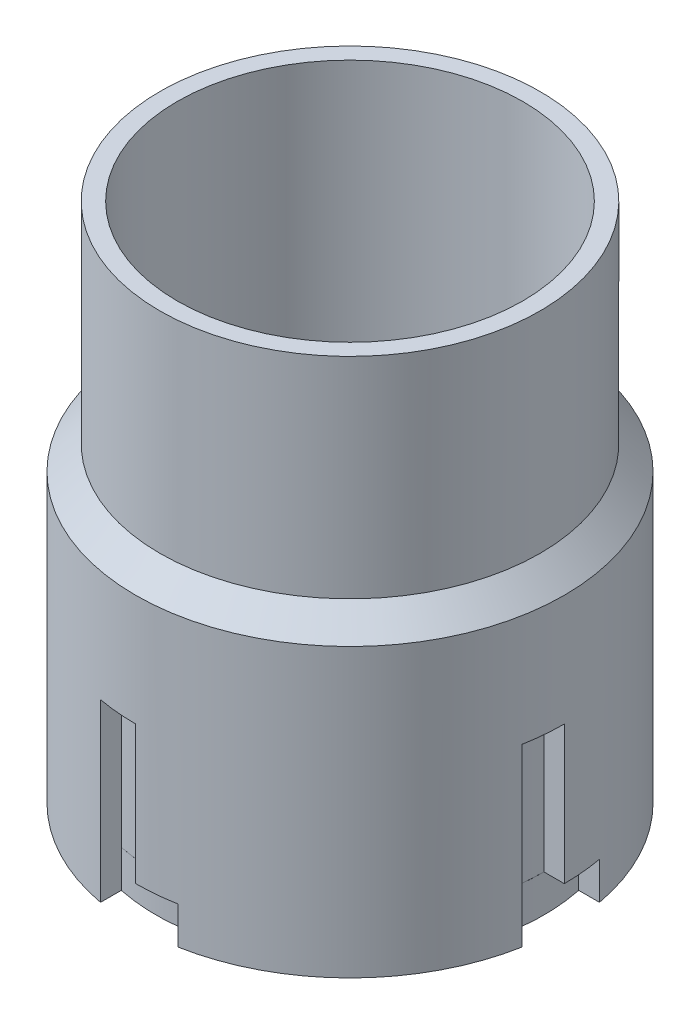
SolidWorks part; units mm, degrees
ref_plane "Front Plane" through (0, 0, 0) normal (0, 0, 1) x (1, 0, 0)
ref_plane "Top Plane" through (0, 0, 0) normal (0, 1, 0) x (1, 0, 0)
ref_plane "Right Plane" through (0, 0, 0) normal (1, 0, 0) x (0, 0, -1)
sketch "Sketch1" plane through (0, 0, 0) normal (0, 1, 0) x (1, 0, 0)
  circle A0 centre (0, 0) radius 39.37
  dimension "D1" = 78.74
extrude "Boss-Extrude1" add sketch "Sketch1" along normal blind 101.6
sketch "Sketch2" plane through (0, 101.6, 0) normal (0, 1, 0) x (1, 0, 0)
  circle A0 centre (0, 0) radius 31.75
extrude "Cut-Extrude1" cut sketch "Sketch2" against normal through all
sketch "Sketch3" plane through (0, 101.6, 0) normal (0, 1, 0) x (1, 0, 0)
  circle A0 centre (0, 0) radius 34.925
  circle A1 centre (0, 0) radius 39.37
  circle A2 centre (0, 0) radius 39.37 construction
extrude "Cut-Extrude2" cut sketch "Sketch3" against normal blind 33.02
sketch "Sketch5" plane through (0, 0, 0) normal (0, -1, 0) x (1, 0, 0)
  line L4 (-7.112, -34.9123) -> (-7.112, -38.7223)
  line L5 (7.112, -34.9123) -> (7.112, -38.7223)
  circle A0 centre (0, 0) radius 39.37 construction
  arc A4 (7.112, -34.9123) -> (-7.112, -34.9123) centre (0, -0.6458) cw
  arc A5 (-7.112, -38.7223) -> (7.112, -38.7223) centre (0, -0.6458) ccw
  dimension "D1" = 3.81
  dimension "D2" = 3.81
  dimension "D3" = 14.224
extrude "Cut-Extrude3" cut sketch "Sketch5" against normal blind 12.7
sketch3d "3DSketch4"
  point P0 (1.3658, 86.1586, 34.8983)
ref_plane "Plane2" through (0, 5.842, 0) normal (0, -1, 0) x (-1, 0, 0)
sketch "Sketch9" plane through (0, 5.842, 0) normal (0, -1, 0) x (-1, 0, 0)
  circle A0 centre (0, 0) radius 39.5588
extrude "Cut-Extrude5" cut sketch "Sketch9" along normal through all
sketch "Sketch10" plane through (0, 5.842, 0) normal (0, -1, 0) x (1, 0, 0)
  circle A0 centre (-22.3186, -27.0798) radius 3.2683
extrude "Boss-Extrude2" add sketch "Sketch10" along normal blind 10.16
sketch "Sketch23" plane through (0, 12.7, 0) normal (0, -1, 0) x (1, 0, 0)
  line L4 (0, -39.37) -> (0, -35.6293)
  line L5 (7.112, -38.7223) -> (7.112, -34.9123)
  arc A0 (-7.112, -38.7223) -> (7.112, -38.7223) centre (0, 0) ccw construction
  arc A1 (0, -39.37) -> (7.112, -38.7223) centre (0, 0) ccw
  arc A2 (7.112, -34.9123) -> (0, -35.6293) centre (0, 0) cw
extrude "Cut-Extrude6" cut sketch "Sketch23" against normal blind 25.4
pattern_circular "CirPattern1" count 4 over 360 about axis through (0, 101.6, 0) along (0, -1, 0) of "Cut-Extrude6", "Cut-Extrude3" reverse direction yes
chamfer "Chamfer1" distance 10 angle 45 1 edges at (0, 68.58, 39.37)
